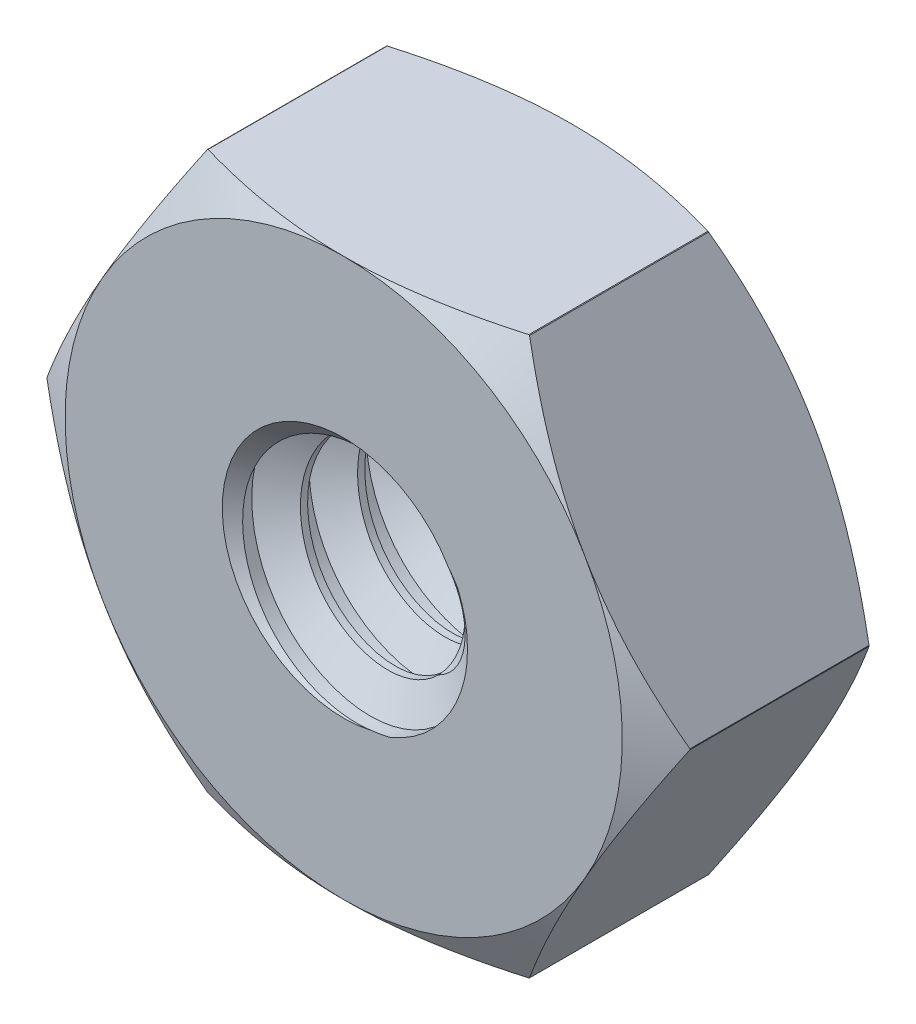
SolidWorks part; units mm, degrees
ref_plane "Front Plane" through (0, 0, 0) normal (0, 0, 1) x (1, 0, 0)
ref_plane "Top Plane" through (0, 0, 0) normal (0, 1, 0) x (1, 0, 0)
ref_plane "Right Plane" through (0, 0, 0) normal (1, 0, 0) x (0, 0, -1)
sketch "Sketch1" plane through (0, 0, 0) normal (0, 1, 0) x (1, 0, 0)
  line L0 (0.3, 0) -> (1.4, 0)
  line L1 (1.6, 0.2) -> (1.6, 1.4)
  line L2 (1.4, 1.6) -> (0.3, 1.6)
  line L3 (0, 1.4268) -> (0, 0.1732)
  line L4 (0, 0.1732) -> (0.3, 0)
  line L5 (0.3, 1.6) -> (0, 1.4268)
  line L6 (1.4, 0) -> (1.6, 0.2)
  line L7 (1.6, 1.4) -> (1.4, 1.6)
  line L8 (2.25, 2.1368) -> (2.25, -0.7185) construction
  point P0 (0, 0)
  point P1 (1.6, 0)
  point P4 (1.6, 1.6)
  point P5 (0, 1.6)
  dimension "D1" = 0.3
  dimension "D2" = 30
  dimension "D3" = 0.3
  dimension "D4" = 30
  dimension "D5" = 1.6
  dimension "D6" = 1.6
  dimension "D7" = 2.25
revolve "Revolve2" add sketch "Sketch1" angle 360 about L8
thread "Thread1" pitch 0.4 start angle 0, offset 1, length 0, pitch 0.4, diameter 1.3
ref_plane "Plane2" through (1.6, 0, 0.8) normal (0, 1, 0) x (1, 0, 0)
sketch "Thread Profile2" plane through (1.6, 0, 0.8) normal (0, 1, 0) x (1, 0, 0)
  line L0 (0, 0) -> (0, 0.4) construction
  line L11 (0, 0) -> (0, 0.35)
  line L12 (0, 0.35) -> (-0.2165, 0.225)
  line L13 (-0.2165, 0.225) -> (-0.2165, 0.125)
  line L15 (-0.2165, 0.125) -> (0, 0)
  line L17 (-0.2165, 0.175) -> (0, 0.175) construction
  point P2 (0, 0)
  dimension "Pitch" = 0.4
  dimension "Profile_Angle" = 60
  dimension "Profile_Land" = 0.1
  dimension "Profile_Height" = 0.2165
sketch "Sketch2" plane through (0, 0, 0) normal (0, 0, 1) x (1, 0, 0)
  line L1 (3.3758, -1.95) -> (4.5017, 0)
  line L2 (4.5017, 0) -> (3.3758, 1.95)
  line L3 (3.3758, 1.95) -> (1.1242, 1.95)
  line L4 (1.1242, 1.95) -> (-0.0017, 0)
  line L5 (-0.0017, 0) -> (1.1242, -1.95)
  line L6 (1.1242, -1.95) -> (3.3758, -1.95)
  circle A0 centre (2.25, 0) radius 1.95 construction
  circle A1 centre (2.25, 0) radius 1.95 construction
extrude "Cut-Extrude1" cut sketch "Sketch2" against normal through all flip side to cut
